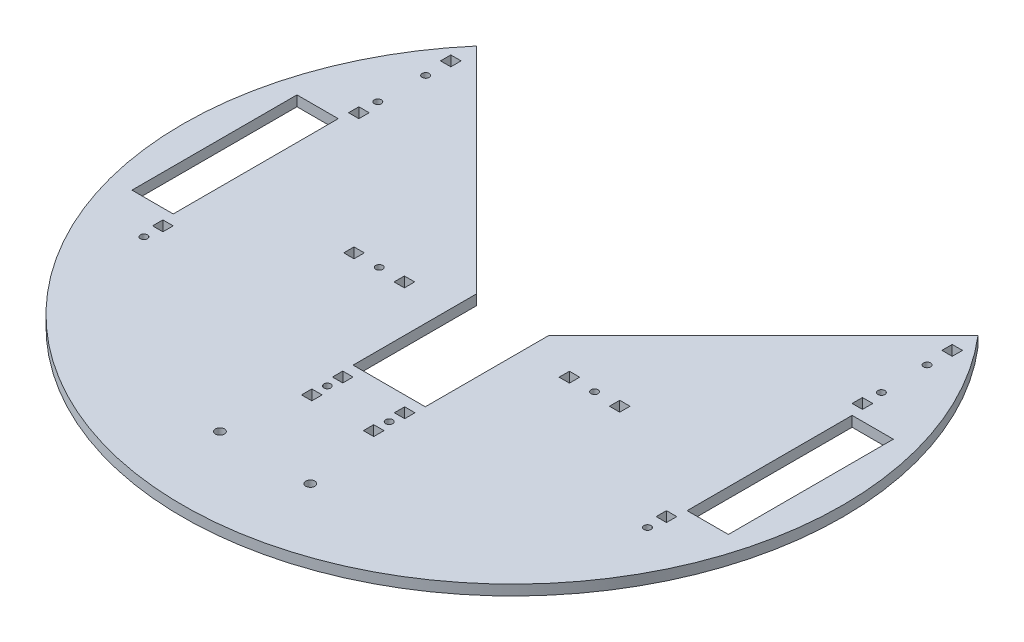
SolidWorks part; units mm, degrees
ref_plane "Front Plane" through (0, 0, 0) normal (0, 0, 1) x (1, 0, 0)
ref_plane "Top Plane" through (0, 0, 0) normal (0, 1, 0) x (1, 0, 0)
ref_plane "Right Plane" through (0, 0, 0) normal (1, 0, 0) x (0, 0, -1)
sketch "Bottom Plate" plane through (0, 0, 0) normal (0, 1, 0) x (1, 0, 0)
  line L0 (22.225, 0) -> (154.3662, 132.1412)
  line L1 (-22.225, 0) -> (-154.3662, 132.1412)
  line L2 (0, 0) -> (0, -203.2) construction
  line L3 (-22.225, 0) -> (-22.225, -76.034)
  line L4 (22.225, 0) -> (22.225, -76.034)
  line L5 (-22.225, 0) -> (22.225, 0) construction
  line L6 (-203.2, 0) -> (197.4825, 0) construction
  line L7 (151.8518, 80.518) -> (151.8518, -80.518) construction
  line L8 (158.2018, -50.8) -> (183.6018, -50.8)
  line L9 (158.2018, -50.8) -> (158.2018, 50.8)
  line L10 (158.2018, 50.8) -> (183.6018, 50.8)
  line L11 (183.6018, -50.8) -> (183.6018, 50.8)
  line L12 (158.2018, -50.8) -> (183.6018, 50.8) construction
  line L13 (158.2018, 50.8) -> (183.6018, -50.8) construction
  line L14 (47.625, -19.05) -> (53.975, -19.05)
  line L15 (47.625, -19.05) -> (47.625, -12.7)
  line L16 (47.625, -12.7) -> (53.975, -12.7)
  line L17 (53.975, -19.05) -> (53.975, -12.7)
  line L18 (47.625, -19.05) -> (53.975, -12.7) construction
  line L19 (47.625, -12.7) -> (53.975, -19.05) construction
  line L20 (151.8518, 72.009) -> (158.2018, 72.009) construction
  line L21 (158.2018, 50.8) -> (158.2018, 80.518) construction
  line L22 (158.2018, -50.8) -> (158.2018, -80.518) construction
  line L23 (151.8518, -63.5) -> (158.2018, -63.5)
  line L24 (151.8518, -63.5) -> (151.8518, -57.15)
  line L25 (151.8518, -57.15) -> (158.2018, -57.15)
  line L26 (158.2018, -63.5) -> (158.2018, -57.15)
  line L27 (151.8518, 63.5) -> (158.2018, 63.5)
  line L28 (158.2018, 63.5) -> (158.2018, 57.15)
  line L29 (151.8518, 63.5) -> (151.8518, 57.15)
  line L30 (151.8518, 57.15) -> (158.2018, 57.15)
  line L31 (-22.225, -76.034) -> (22.225, -76.034)
  line L32 (151.8518, 80.518) -> (158.2018, 80.518) construction
  line L33 (157.5412, 113.0912) -> (157.5412, 92.2632) construction
  line L34 (151.1912, 113.0912) -> (157.5412, 113.0912)
  line L35 (151.1912, 113.0912) -> (151.1912, 119.4412)
  line L36 (151.1912, 119.4412) -> (157.5412, 119.4412)
  line L37 (154.3662, 132.1412) -> (154.3662, 92.2632) construction
  line L38 (157.5412, 113.0912) -> (157.5412, 119.4412)
  line L39 (151.1912, 113.0912) -> (157.5412, 119.4412) construction
  line L40 (151.1912, 119.4412) -> (157.5412, 113.0912) construction
  line L41 (157.5412, 92.2632) -> (151.1912, 92.2632) construction
  line L42 (151.1912, 92.2632) -> (151.1912, 128.9662) construction
  line L43 (50.8, -15.875) -> (100.8077, -15.875) construction
  line L44 (78.613, -19.05) -> (84.963, -19.05)
  line L45 (78.613, -19.05) -> (78.613, -12.7)
  line L46 (78.613, -12.7) -> (84.963, -12.7)
  line L47 (84.963, -19.05) -> (84.963, -12.7)
  line L48 (78.613, -19.05) -> (84.963, -12.7) construction
  line L49 (78.613, -12.7) -> (84.963, -19.05) construction
  line L50 (-22.225, -76.034) -> (-22.225, -107.784) construction
  line L51 (27.813, -152.4) -> (-27.813, -152.4) construction
  line L52 (-19.05, -82.384) -> (-19.05, -107.784) construction
  line L53 (-22.225, -82.384) -> (-15.875, -82.384)
  line L54 (-22.225, -82.384) -> (-22.225, -88.734)
  line L55 (-22.225, -88.734) -> (-15.875, -88.734)
  line L56 (-15.875, -82.384) -> (-15.875, -88.734)
  line L57 (-15.875, -101.434) -> (-22.225, -101.434)
  line L58 (-15.875, -101.434) -> (-15.875, -107.784)
  line L59 (-15.875, -107.784) -> (-22.225, -107.784)
  line L60 (-22.225, -101.434) -> (-22.225, -107.784)
  line L61 (19.05, -82.384) -> (19.05, -107.784) construction
  line L62 (22.225, -76.034) -> (22.225, -107.784) construction
  line L63 (22.225, -101.434) -> (22.225, -107.784)
  line L64 (15.875, -107.784) -> (22.225, -107.784)
  line L65 (15.875, -101.434) -> (15.875, -107.784)
  line L66 (15.875, -101.434) -> (22.225, -101.434)
  line L67 (15.875, -82.384) -> (15.875, -88.734)
  line L68 (22.225, -88.734) -> (15.875, -88.734)
  line L69 (22.225, -82.384) -> (22.225, -88.734)
  line L70 (22.225, -82.384) -> (15.875, -82.384)
  line L71 (-78.613, -12.7) -> (-84.963, -19.05) construction
  line L72 (-78.613, -19.05) -> (-84.963, -12.7) construction
  line L73 (151.8518, -80.518) -> (158.2018, -80.518) construction
  line L74 (-47.625, -12.7) -> (-53.975, -19.05) construction
  line L75 (-47.625, -19.05) -> (-53.975, -12.7) construction
  line L76 (-84.963, -19.05) -> (-84.963, -12.7)
  line L77 (-78.613, -12.7) -> (-84.963, -12.7)
  line L78 (-78.613, -19.05) -> (-78.613, -12.7)
  line L79 (-78.613, -19.05) -> (-84.963, -19.05)
  line L80 (-53.975, -19.05) -> (-53.975, -12.7)
  line L81 (-47.625, -12.7) -> (-53.975, -12.7)
  line L82 (-47.625, -19.05) -> (-47.625, -12.7)
  line L83 (-47.625, -19.05) -> (-53.975, -19.05)
  line L84 (-158.2018, 50.8) -> (-183.6018, -50.8) construction
  line L85 (-158.2018, -50.8) -> (-183.6018, 50.8) construction
  line L86 (-183.6018, -50.8) -> (-183.6018, 50.8)
  line L87 (-158.2018, -50.8) -> (-158.2018, 50.8)
  line L88 (-158.2018, -63.5) -> (-158.2018, -57.15)
  line L89 (-151.8518, -57.15) -> (-158.2018, -57.15)
  line L90 (-151.8518, -63.5) -> (-151.8518, -57.15)
  line L91 (-151.8518, -63.5) -> (-158.2018, -63.5)
  line L92 (-158.2018, -50.8) -> (-183.6018, -50.8)
  line L93 (-158.2018, 50.8) -> (-183.6018, 50.8)
  line L94 (-151.8518, 57.15) -> (-158.2018, 57.15)
  line L95 (-151.8518, 63.5) -> (-151.8518, 57.15)
  line L96 (-158.2018, 63.5) -> (-158.2018, 57.15)
  line L99 (-151.8518, 63.5) -> (-158.2018, 63.5)
  line L101 (-151.1912, 119.4412) -> (-157.5412, 113.0912) construction
  line L102 (-151.1912, 113.0912) -> (-157.5412, 119.4412) construction
  line L103 (-157.5412, 113.0912) -> (-157.5412, 119.4412)
  line L104 (-151.1912, 119.4412) -> (-157.5412, 119.4412)
  line L105 (-151.1912, 113.0912) -> (-151.1912, 119.4412)
  line L106 (-151.1912, 113.0912) -> (-157.5412, 113.0912)
  arc A0 (-154.3662, 132.1412) -> (154.3662, 132.1412) centre (0, 0) ccw
  circle A1 centre (155.0268, 72.009) radius 2.159
  circle A2 centre (155.0268, -72.009) radius 2.159
  circle A3 centre (154.3662, 100.7722) radius 2.159
  circle A4 centre (66.294, -15.875) radius 2.159
  circle A5 centre (-19.05, -95.084) radius 2.159
  circle A6 centre (27.813, -152.4) radius 2.794
  circle A7 centre (-27.813, -152.4) radius 2.794
  circle A8 centre (19.05, -95.084) radius 2.159
  circle A9 centre (-66.294, -15.875) radius 2.159
  circle A10 centre (-155.0268, -72.009) radius 2.159
  circle A11 centre (-155.0268, 72.009) radius 2.159
  circle A12 centre (-154.3662, 100.7722) radius 2.159
  point P2 (154.3662, 116.2662)
  point P13 (170.9018, 0)
  point P51 (81.788, -15.875)
  point P74 (0, -152.4)
  point P99 (-81.788, -15.875)
  point P106 (-170.9018, 0)
  point P129 (-154.3662, 116.2662)
  dimension "D1" = 406.4
  dimension "D11" = 4.318
  dimension "D12" = 6.35
  dimension "D14" = 6.35
  dimension "D17" = 6.35
  dimension "D20" = 4.318
  dimension "D21" = 6.35
  dimension "D24" = 4.318
  dimension "D28" = 10.16
  dimension "D35" = 4.318
  dimension "D15" = 5.588
  dimension "D36" = 5.588
  dimension "D3" = 44.45
  dimension "D4" = 101.6
  dimension "D5" = 25.4
  dimension "D6" = 12.7
  dimension "D7" = 6.35
  dimension "D8" = 6.35
  dimension "D9" = 25.4
  dimension "D10" = 6.35
  dimension "D13" = 6.35
  dimension "D16" = 6.35
  dimension "D18" = 6.35
  dimension "D19" = 12.7
  dimension "D22" = 10.16
  dimension "D23" = 12.7
  dimension "D25" = 10.16
  dimension "D26" = 6.35
  dimension "D27" = 6.35
  dimension "D29" = 6.35
  dimension "D30" = 6.35
  dimension "D31" = 6.35
  dimension "D32" = 12.7
  dimension "D33" = 6.35
  dimension "D34" = 6.35
  dimension "D37" = 55.626
  dimension "D38" = 50.8
  dimension "D39" = 45
extrude "Boss-Extrude1" add sketch "Bottom Plate" against normal blind 6.35
equation "\"Ball Diameter\"= 1.75in"
equation "\"D3@Bottom Plate\"=\"Ball Diameter\""
equation "\"Sheet Thickness\"= 0.25in"
equation "\"D13@Bottom Plate\"=\"Sheet Thickness\""
equation "\"D10@Bottom Plate\"=\"Sheet Thickness\""
equation "\"D8@Bottom Plate\"=\"Sheet Thickness\""
equation "\"D7@Bottom Plate\"=\"Sheet Thickness\""
equation "\"Screw Diameter\"= .17in"
equation "\"D11@Bottom Plate\"=\"Screw Diameter\""
equation "\"Robot Diameter\"= 16in"
equation "\"D1@Bottom Plate\"=\"Robot Diameter\""
equation "\"D16@Bottom Plate\"=\"Sheet Thickness\""
equation "\"D18@Bottom Plate\"=\"Sheet Thickness\""
equation "\"D20@Bottom Plate\"=\"Screw Diameter\""
equation "\"D24@Bottom Plate\"=\"Screw Diameter\""
equation "\"D26@Bottom Plate\"=\"Sheet Thickness\""
equation "\"D27@Bottom Plate\"=\"Sheet Thickness\""
equation "\"D29@Bottom Plate\"=\"Sheet Thickness\""
equation "\"D30@Bottom Plate\"=\"Sheet Thickness\""
equation "\"D33@Bottom Plate\"=\"Sheet Thickness\""
equation "\"D34@Bottom Plate\"=\"Sheet Thickness\""
equation "\"D35@Bottom Plate\"=\"Screw Diameter\""
equation "\"Castor Screw Diameter\"= 0.22in"
equation "\"D15@Bottom Plate\"=\"Castor Screw Diameter\""
equation "\"D36@Bottom Plate\"=\"Castor Screw Diameter\""
equation "\"Wheel Diameter\" = 4in"
equation "\"D4@Bottom Plate\"=\"Wheel Diameter\""
